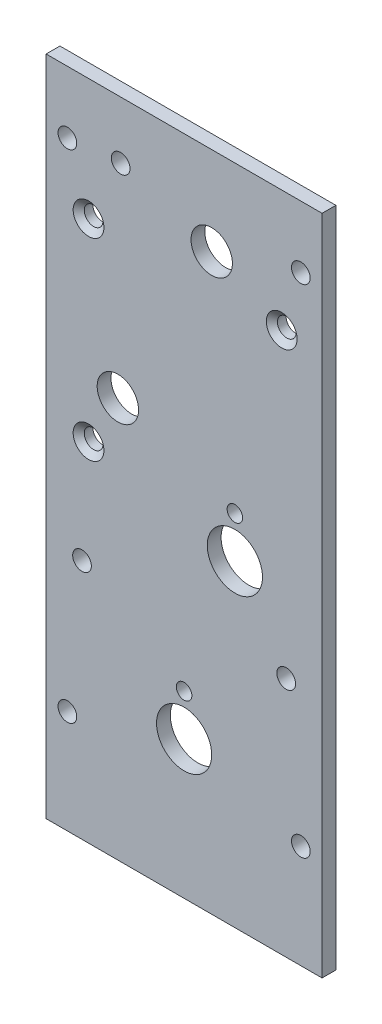
SolidWorks part; units mm, degrees
material "Acrylic (Medium-high impact)"
ref_plane "Front Plane" through (0, 0, 0) normal (0, 0, 1) x (1, 0, 0)
ref_plane "Top Plane" through (0, 0, 0) normal (0, 1, 0) x (1, 0, 0)
ref_plane "Right Plane" through (0, 0, 0) normal (1, 0, 0) x (0, 0, -1)
sketch "Sketch1" plane through (0, 0, 0) normal (0, 0, 1) x (1, 0, 0)
  line L8 (31.75, -152.4) -> (31.75, 0)
  line L9 (31.75, 0) -> (-31.75, 0)
  line L10 (-31.75, 0) -> (-31.75, -152.4)
  line L11 (-31.75, -152.4) -> (31.75, -152.4)
extrude "Boss-Extrude1" add sketch "Sketch1" against normal blind 3.175
hole_wizard "#6 Clearance Hole1" positions "Sketch3" profile "Sketch2" hole size "#6" standard "ANSI Inch" end condition up to next
sketch "Sketch3" plane through (0, 0, 0) normal (0, 0, 1) x (1, 0, 0)
  point P0 (-26.8605, -14.2875)
  point P2 (26.8605, -14.2875)
  point P4 (26.8605, -128.5875)
  point P6 (-26.8605, -128.5875)
sketch "Sketch2" plane through (-26.8605, -14.2875, 0) normal (1, 0, 0) x (0, -1, 0)
  line L0 (0, 0) -> (0, 3.175)
  line L1 (0, 3.175) -> (2.1526, 3.175)
  line L2 (2.1526, 3.175) -> (2.1526, 0)
  line L5 (2.1526, 0) -> (0, 0)
  line L11 (0, -6.35) -> (0, 107.95) construction
  dimension "Thru Hole Dia." = 4.3053
  dimension "Thru Hole Depth" = 3.175
hole_wizard "#6 Clearance Hole2" positions "Sketch5" profile "Sketch4" hole size "#6" standard "ANSI Inch" end condition up to next
sketch "Sketch5" plane through (0, 0, 0) normal (0, 0, 1) x (1, 0, 0)
  point P0 (-23.495, -96.8375)
  point P2 (23.495, -96.8375)
  point P4 (-14.605, -13.208)
sketch "Sketch4" plane through (-23.495, -96.8375, 0) normal (1, 0, 0) x (0, -1, 0)
  line L0 (0, 0) -> (0, 3.175)
  line L1 (0, 3.175) -> (2.1526, 3.175)
  line L2 (2.1526, 3.175) -> (2.1526, 0)
  line L5 (2.1526, 0) -> (0, 0)
  line L11 (0, -6.35) -> (0, 107.95) construction
  dimension "Thru Hole Dia." = 4.3053
  dimension "Thru Hole Depth" = 3.175
hole_wizard "1/2 (0.5) Diameter Hole1" positions "Sketch7" profile "Sketch6" hole size "1/2" standard "ANSI Inch" end condition up to next
sketch "Sketch7" plane through (0, 0, 0) normal (0, 0, 1) x (1, 0, 0)
  point P4 (11.684, -79.375)
  point P6 (0, -120.65)
sketch "Sketch6" plane through (11.684, -79.375, 0) normal (1, 0, 0) x (0, -1, 0)
  line L0 (0, 0) -> (0, 3.175)
  line L1 (0, 3.175) -> (6.35, 3.175)
  line L2 (6.35, 3.175) -> (6.35, 0)
  line L5 (6.35, 0) -> (0, 0)
  line L11 (0, -6.35) -> (0, 107.95) construction
  dimension "Thru Hole Dia." = 12.7
  dimension "Thru Hole Depth" = 3.175
hole_wizard "9/64 (0.14063) Diameter Hole1" positions "Sketch9" profile "Sketch8" hole size "9/64" standard "ANSI Inch" end condition up to next
sketch "Sketch9" plane through (0, 0, 0) normal (0, 0, 1) x (1, 0, 0)
  point P0 (0, -111.125)
  point P2 (11.684, -69.85)
sketch "Sketch8" plane through (0, -111.125, 0) normal (1, 0, 0) x (0, -1, 0)
  line L0 (0, 0) -> (0, 3.175)
  line L1 (0, 3.175) -> (1.786, 3.175)
  line L2 (1.786, 3.175) -> (1.786, 0)
  line L5 (1.786, 0) -> (0, 0)
  line L11 (0, -6.35) -> (0, 107.95) construction
  dimension "Thru Hole Dia." = 3.572
  dimension "Thru Hole Depth" = 3.175
hole_wizard "3/8 (0.375) Diameter Hole1" positions "Sketch11" profile "Sketch10" hole size "3/8" standard "ANSI Inch" end condition up to next
sketch "Sketch11" plane through (0, 0, 0) normal (0, 0, 1) x (1, 0, 0)
  point P0 (-15.24, -60.325)
  point P2 (6.35, -20.32)
sketch "Sketch10" plane through (-15.24, -60.325, 0) normal (1, 0, 0) x (0, -1, 0)
  line L0 (0, 0) -> (0, 3.175)
  line L1 (0, 3.175) -> (4.7625, 3.175)
  line L2 (4.7625, 3.175) -> (4.7625, 0)
  line L5 (4.7625, 0) -> (0, 0)
  line L11 (0, -6.35) -> (0, 107.95) construction
  dimension "Thru Hole Dia." = 9.525
  dimension "Thru Hole Depth" = 3.175
hole_wizard "CSK for #6 Flat Head Machine Screw (100)1" positions "Sketch12" profile "Sketch13" countersink size "#6" standard "ANSI Inch" end condition up to next
sketch "Sketch12" plane through (0, 0, 0) normal (0, 0, 1) x (1, 0, 0)
  circle A0 centre (-21.99, -72.39) radius 2.15 construction
  circle A1 centre (-21.99, -27.94) radius 2.15 construction
  circle A2 centre (22.46, -27.94) radius 2.15 construction
  point P0 (-21.99, -72.39)
  point P5 (-21.99, -27.94)
  point P7 (22.46, -27.94)
  point P10 (0, 0)
  point P13 (0, 0)
sketch "Sketch13" plane through (-21.99, -72.39, 0) normal (1, 0, 0) x (0, -1, 0)
  line L0 (0, 0) -> (0, 3.175)
  line L1 (0, 3.175) -> (2.1526, 3.175)
  line L2 (2.1526, 3.175) -> (2.1526, 1.1669)
  line L3 (2.1526, 1.1669) -> (3.5433, 0)
  line L5 (3.5433, 0) -> (0, 0)
  line L6 (-2.1526, 1.1669) -> (-3.5433, 0) construction
  line L11 (0, -6.35) -> (0, 107.95) construction
  dimension "Thru Hole Dia." = 4.3053
  dimension "Thru Hole Depth" = 3.175
  dimension "Near C'Sink Dia." = 7.0866
  dimension "Near C'Sink Angle" = 100
